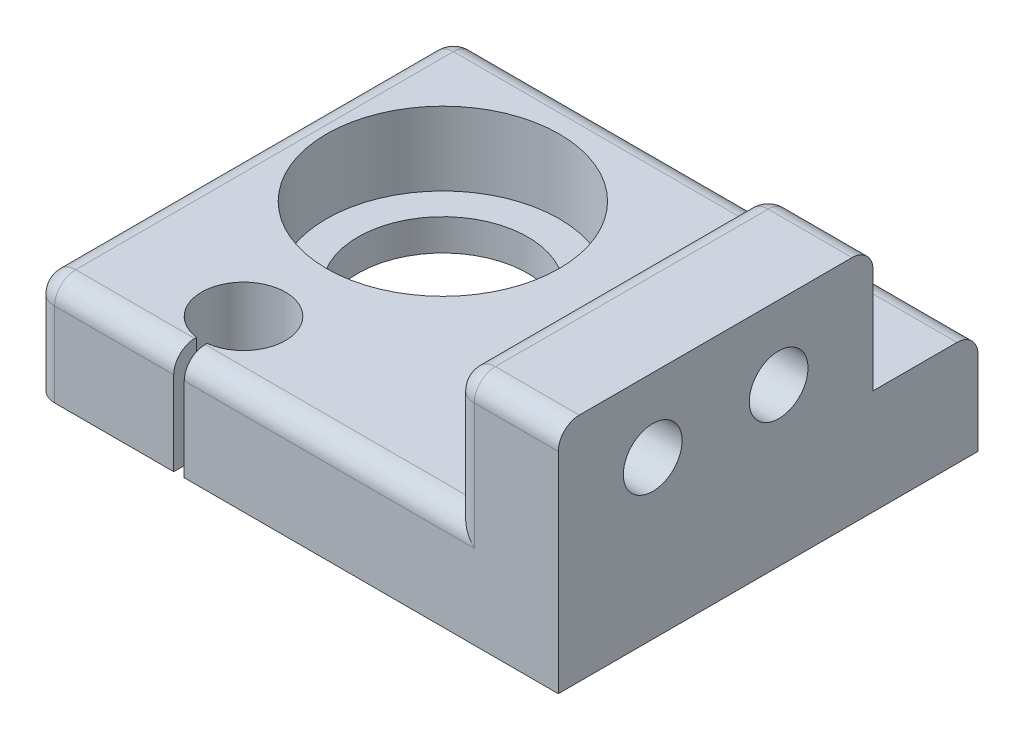
SolidWorks part; units mm, degrees
ref_plane "Front Plane" through (0, 0, 0) normal (0, 0, 1) x (1, 0, 0)
ref_plane "Top Plane" through (0, 0, 0) normal (0, 1, 0) x (1, 0, 0)
ref_plane "Right Plane" through (0, 0, 0) normal (1, 0, 0) x (0, 0, -1)
sketch "Sketch1" plane through (0, 0, 0) normal (0, 1, 0) x (1, 0, 0)
  line L0 (13.85, -14.85) -> (13.85, -33.85) construction
  line L1 (0, 0) -> (50, 0)
  line L2 (0, 0) -> (0, -40)
  line L3 (0, -40) -> (50, -40)
  line L4 (50, 0) -> (50, -40)
  line L5 (13.85, -33.85) -> (13.85, -40) construction
  line L6 (13.85, -14.85) -> (13.85, 0) construction
  line L8 (13.35, -37.8186) -> (14.35, -37.8186)
  line L9 (13.35, -37.8186) -> (13.35, -40)
  line L10 (13.35, -40) -> (14.35, -40)
  line L11 (14.35, -37.8186) -> (14.35, -40)
  circle A0 centre (13.85, -33.85) radius 4
  circle A1 centre (13.85, -14.85) radius 8.1
  circle A2 centre (13.85, -14.85) radius 11.1 construction
  point P16 (12.5552, -37.8186)
  point P17 (13.0074, -40)
  dimension "D3" = 8
  dimension "D4" = 6.15
  dimension "D6" = 22.2
  dimension "D7" = 3
  dimension "D1" = 40
  dimension "D2" = 50
  dimension "D5" = 19
  dimension "D8" = 1
  dimension "D9" = 13.85
extrude "Boss-Extrude1" add sketch "Sketch1" along normal blind 10 contours A0 L1 L2 L3 L4 A1 region at (26.6554, 0, 20.1863)
sketch "Sketch2" plane through (0, 10, 0) normal (0, 1, 0) x (1, 0, 0)
  circle A0 centre (13.85, -14.85) radius 11.1 construction
  circle A1 centre (13.85, -14.85) radius 11.1
extrude "Cut-Extrude1" cut sketch "Sketch2" against normal blind 7
sketch "Sketch3" plane through (0, 0, 40) normal (0, 0, -1) x (-1, 0, 0)
  line L1 (-50, 10) -> (-40, 10)
  line L2 (-50, 10) -> (-50, 22)
  line L3 (-50, 22) -> (-40, 22)
  line L4 (-40, 10) -> (-40, 22)
  dimension "D1" = 12
  dimension "D2" = 10
extrude "Boss-Extrude2" add sketch "Sketch3" along normal blind 30
sketch "Sketch4" plane through (40, 0, 0) normal (-1, 0, 0) x (0, 0, 1)
  line L0 (10, 15) -> (19, 15) construction
  line L1 (10, 10) -> (10, 22) construction
  line L2 (19, 15) -> (31, 15) construction
  line L3 (31, 15) -> (40, 15) construction
  line L4 (40, 10) -> (40, 22) construction
  line L5 (0, 10) -> (40, 10) construction
  circle A0 centre (19, 15) radius 2.8
  circle A1 centre (31, 15) radius 2.8
  dimension "D1" = 5.6
  dimension "D2" = 12
  dimension "D3" = 5
extrude "Cut-Extrude2" cut sketch "Sketch4" against normal through all
sketch "Sketch5" plane through (40, 0, 0) normal (-1, 0, 0) x (0, 0, 1)
  circle A0 centre (19, 15) radius 4.3
  circle A1 centre (31, 15) radius 4.3
  dimension "D1" = 8.6
extrude "Cut-Extrude3" cut sketch "Sketch5" against normal blind 6
fillet "Fillet1" radius 2 11 edges at (45, 22, 10) (40, 16, 10) (45, 22, 40) (40, 22, 25) (40, 16, 40) (6.675, 10, 40) (27.175, 10, 40) (0, 5, 40) (0, 10, 20) (25, 10, 0) (0, 5, 0)
